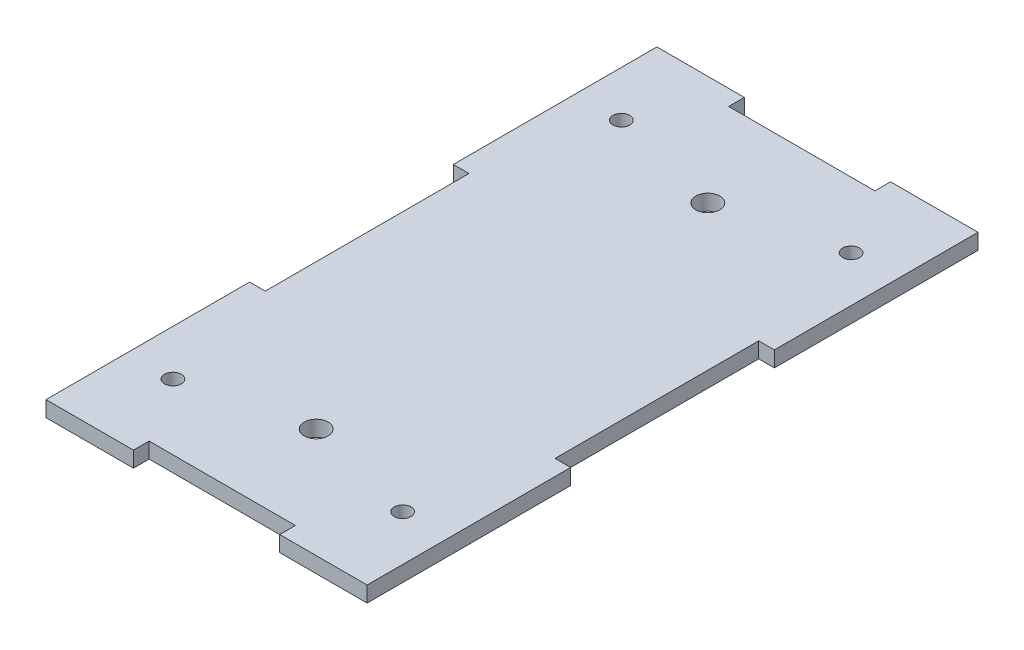
SolidWorks part; units mm, degrees
ref_plane "Front Plane" through (0, 0, 0) normal (0, 0, 1) x (1, 0, 0)
ref_plane "Top Plane" through (0, 0, 0) normal (0, 1, 0) x (1, 0, 0)
ref_plane "Right Plane" through (0, 0, 0) normal (1, 0, 0) x (0, 0, -1)
sketch "Sketch1" plane through (0, 0, 0) normal (0, 1, 0) x (1, 0, 0)
  line L0 (-30.75, 58.5) -> (-30.75, 19.5)
  line L1 (-30.75, -58.5) -> (30.75, -58.5) construction
  line L2 (-30.75, -58.5) -> (-30.75, 58.5) construction
  line L3 (-30.75, 58.5) -> (30.75, 58.5) construction
  line L4 (30.75, -58.5) -> (30.75, 58.5) construction
  line L5 (-30.75, -58.5) -> (30.75, 58.5) construction
  line L6 (-30.75, 58.5) -> (30.75, -58.5) construction
  line L7 (-27.75, -55.5) -> (27.75, -55.5) construction
  line L8 (-27.75, -55.5) -> (-27.75, 55.5) construction
  line L9 (-27.75, 55.5) -> (27.75, 55.5) construction
  line L10 (27.75, -55.5) -> (27.75, 55.5) construction
  line L11 (-27.75, -55.5) -> (27.75, 55.5) construction
  line L12 (-27.75, 55.5) -> (27.75, -55.5) construction
  line L13 (-30.75, 19.5) -> (-27.75, 19.5)
  line L14 (-27.75, 19.5) -> (-27.75, -19.5)
  line L15 (-27.75, -19.5) -> (-30.75, -19.5)
  line L16 (-30.75, -19.5) -> (-30.75, -58.5)
  line L17 (-30.75, -58.5) -> (-14, -58.5)
  line L18 (-14, -58.5) -> (-14, -55.5)
  line L19 (-14, -55.5) -> (14, -55.5)
  line L20 (14, -55.5) -> (14, -58.5)
  line L21 (14, -58.5) -> (30.75, -58.5)
  line L22 (30.75, -58.5) -> (30.75, -19.5)
  line L23 (30.75, -19.5) -> (27.75, -19.5)
  line L24 (27.75, -19.5) -> (27.75, 19.5)
  line L25 (27.75, 19.5) -> (30.75, 19.5)
  line L26 (30.75, 19.5) -> (30.75, 58.5)
  line L27 (30.75, 58.5) -> (14, 58.5)
  line L28 (14, 58.5) -> (14, 55.5)
  line L29 (14, 55.5) -> (-14, 55.5)
  line L30 (-14, 55.5) -> (-14, 58.5)
  line L31 (-14, 58.5) -> (-30.75, 58.5)
  line L32 (0, -37.5) -> (0, 37.5) construction
  line L33 (-22, 42.94) -> (22, 42.94) construction
  line L34 (22, 42.94) -> (22, -42.94) construction
  circle A0 centre (0, 37.5) radius 2.3
  circle A1 centre (0, -37.5) radius 2.3
  circle A2 centre (-22, -42.94) radius 1.6092
  circle A3 centre (22, -42.94) radius 1.6092
  circle A4 centre (22, 42.94) radius 1.6092
  circle A5 centre (-22, 42.94) radius 1.6092
  point P0 (0, 0)
  point P6 (0, 0)
  point P31 (0, 0)
  point P40 (22, 0)
  point P41 (0, 42.94)
  dimension "D6" = 4.6
  dimension "D1" = 61.5
  dimension "D2" = 117
  dimension "D3" = 3
  dimension "D4" = 3
  dimension "D5" = 75
  dimension "D7" = 44
  dimension "D8" = 85.88
  dimension "D9" = 28
extrude "Boss-Extrude1" add sketch "Sketch1" along normal blind 3
